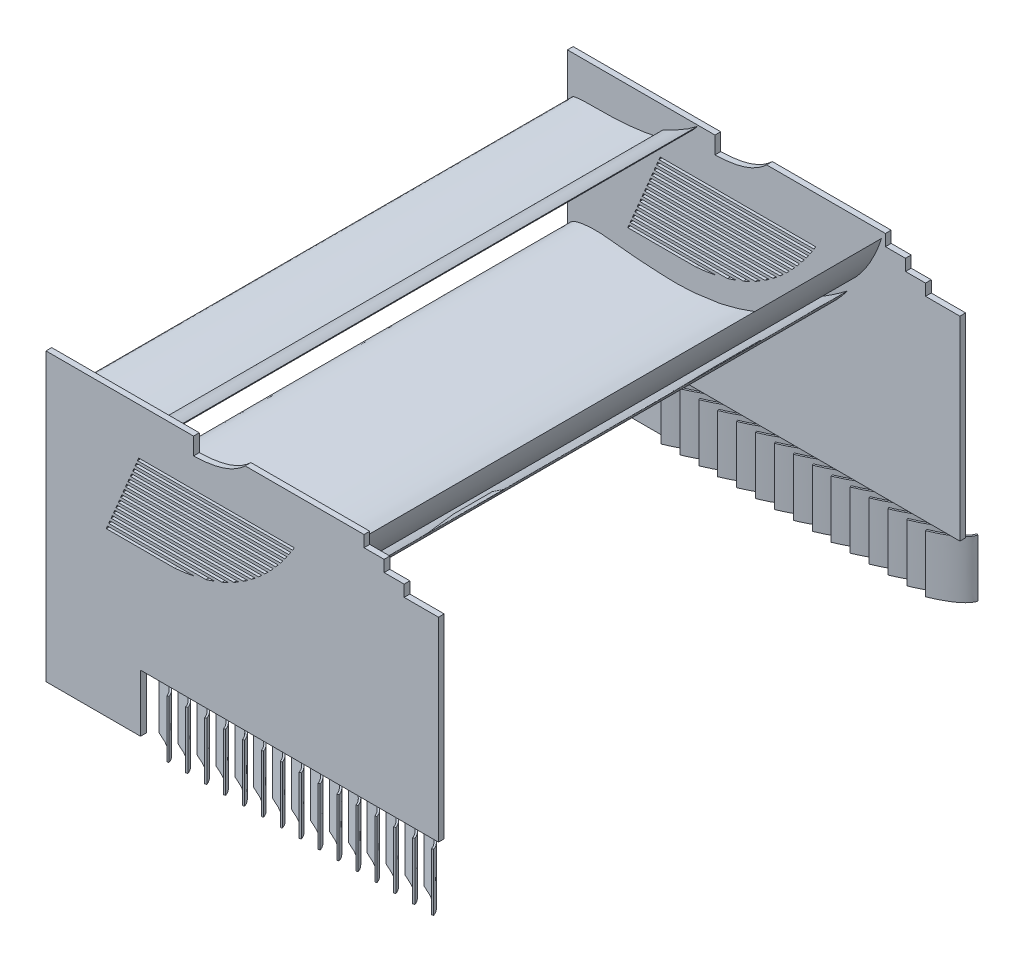
SolidWorks part; units mm, degrees
ref_plane "Front Plane" through (0, 0, 0) normal (0, 0, 1) x (1, 0, 0)
ref_plane "Top Plane" through (0, 0, 0) normal (0, 1, 0) x (1, 0, 0)
ref_plane "Right Plane" through (0, 0, 0) normal (1, 0, 0) x (0, 0, -1)
sketch "Sketch1" plane through (0, 0, 0) normal (0, 0, 1) x (1, 0, 0)
  line L0 (46.9575, 64.3181) -> (1074.8558, 208.7798) construction
sketch "Sketch2" plane through (0, 0, 0) normal (0, 0, 1) x (1, 0, 0)
  line L0 (0, 0) -> (400, 0) construction
  line L1 (0, 0) -> (399.6225, 66.8739) construction
  line L2 (0, 66.8739) -> (0, -66.8739) construction
  line L3 (10.0115, 66.8739) -> (10.0115, -116.1581) construction
  line L4 (20.0229, 66.8739) -> (20.0229, -116.1581) construction
  line L5 (30.0344, 66.8739) -> (30.0344, -116.1581) construction
  line L6 (40.0459, 66.8739) -> (40.0459, -116.1581) construction
  line L7 (50.0573, 66.8739) -> (50.0573, -116.1581) construction
  line L8 (60.0688, 66.8739) -> (60.0688, -116.1581) construction
  line L9 (70.0803, 66.8739) -> (70.0803, -116.1581) construction
  line L10 (80.0918, 66.8739) -> (80.0918, -116.1581) construction
  line L11 (90.1032, 66.8739) -> (90.1032, -116.1581) construction
  line L12 (100.1147, 66.8739) -> (100.1147, -116.1581) construction
  line L13 (110.1262, 66.8739) -> (110.1262, -116.1581) construction
  line L14 (120.1376, 66.8739) -> (120.1376, -116.1581) construction
  line L15 (130.1491, 66.8739) -> (130.1491, -116.1581) construction
  line L16 (140.1606, 66.8739) -> (140.1606, -116.1581) construction
  line L17 (150.172, 66.8739) -> (150.172, -116.1581) construction
  line L18 (160.1835, 66.8739) -> (160.1835, -116.1581) construction
  line L19 (170.195, 66.8739) -> (170.195, -116.1581) construction
  line L20 (180.2064, 66.8739) -> (180.2064, -116.1581) construction
  line L21 (190.2179, 66.8739) -> (190.2179, -116.1581) construction
  line L22 (200.2294, 66.8739) -> (200.2294, -116.1581) construction
  line L23 (210.2408, 66.8739) -> (210.2408, -116.1581) construction
  line L24 (220.2523, 66.8739) -> (220.2523, -116.1581) construction
  line L25 (230.2638, 66.8739) -> (230.2638, -116.1581) construction
  line L26 (240.2753, 66.8739) -> (240.2753, -116.1581) construction
  line L27 (250.2867, 66.8739) -> (250.2867, -116.1581) construction
  line L28 (260.2982, 66.8739) -> (260.2982, -116.1581) construction
  line L29 (270.3097, 66.8739) -> (270.3097, -116.1581) construction
  line L30 (280.3211, 66.8739) -> (280.3211, -116.1581) construction
  line L31 (290.3326, 66.8739) -> (290.3326, -116.1581) construction
  line L32 (300.3441, 66.8739) -> (300.3441, -116.1581) construction
  line L33 (310.3555, 66.8739) -> (310.3555, -116.1581) construction
  line L34 (320.367, 66.8739) -> (320.367, -116.1581) construction
  line L35 (330.3785, 66.8739) -> (330.3785, -116.1581) construction
  line L36 (340.3899, 66.8739) -> (340.3899, -116.1581) construction
  line L37 (350.4014, 66.8739) -> (350.4014, -116.1581) construction
  line L38 (360.4129, 66.8739) -> (360.4129, -116.1581) construction
  line L39 (370.4243, 66.8739) -> (370.4243, -116.1581) construction
  line L40 (380.4358, 66.8739) -> (380.4358, -116.1581) construction
  line L41 (390.4473, 66.8739) -> (390.4473, -116.1581) construction
  line L42 (400.4588, 66.8739) -> (400.4588, -116.1581) construction
  line L43 (836.1007, 66.8739) -> (-36.8556, 66.8739) construction
  line L44 (389.6225, 76.8739) -> (409.6225, 76.8739) construction
  line L45 (399.6225, 90.7703) -> (399.6225, 62.9774) construction
  line L46 (548.1427, 255.362) -> (478.7399, 156.2446) construction
  line L47 (488.7399, 146.2766) -> (482.6971, 142.1346) construction
  line L48 (389.6225, 76.8739) -> (488.7399, 146.2766) construction
  line L51 (488.7399, 194.8045) -> (488.7399, 123.7678) construction
  line L52 (478.7399, 201.6203) -> (478.7399, 116.9521) construction
  line L53 (478.7399, 156.2446) -> (614.5057, 156.2446) construction
  line L54 (389.6225, 83.3039) -> (389.6225, -27.4023) construction
  line L55 (478.7399, 146.2446) -> (614.5057, 146.2446) construction
  spline S0 degree 3 poles (8.4176, 12.2629) (-5.1, -0.6947) (8.0175, -15.4806) (19.5512, -21.724) (30.0167, -25.3022) (39.86, -28.8642) (50.0404, -30.6629) (60.0706, -32.2577) (70.0139, -34.2177) (80.101, -34.56) (90.0931, -35.3652) (100.112, -35.9529) (110.1282, -35.5072) (120.1532, -35.21) (130.1503, -34.2298) (140.19, -33.4102) (150.1782, -31.9134) (160.1704, -30.3713) (170.2408, -29.1636) (180.2083, -27.151) (190.2638, -25.3061) (200.2392, -22.8725) (210.2446, -20.4291) (220.2329, -17.8951) (230.3811, -15.7054) (240.3519, -12.3911) (253.5512, -7.3696) (266.9476, -2.8065) (280.4369, 1.6366) (290.3614, 5.8195) (300.4407, 10.0322) (310.3048, 14.8841) (323.8214, 20.8842) (337.3023, 27.2498) (350.2747, 34.8502) (364.0374, 41.2007) (378.0734, 50.4319) (389.2687, 56.9917) (404.9331, 70.6704) (388.8931, 60.8973) (380.9617, 56.8333) (370.3166, 52.1732) (360.4136, 47.7491) (350.4697, 43.0754) (340.4967, 38.8332) (330.4052, 35.261) (320.3498, 31.8494) (310.3583, 28.3259) (300.4869, 24.6622) (290.3218, 22.3006) (280.2904, 19.7619) (270.4267, 16.765) (260.336, 15.0613) (250.2769, 13.9588) (240.2662, 12.5783) (230.2787, 11.0679) (220.2867, 9.6964) (210.2433, 9.2404) (200.2287, 9.0345) (190.217, 8.2792) (180.2125, 9.1624) (170.1842, 8.7285) (160.1865, 9.5822) (150.1678, 9.9892) (140.1635, 10.7007) (130.146, 11.2145) (120.1214, 11.8409) (110.1328, 12.9697) (100.1148, 13.8501) (90.0938, 14.7159) (80.0796, 15.8427) (56.9177, 18.8475) (32.3828, 18.9634) (8.4176, 12.2629) (-5.1, -0.6947) (8.0175, -15.4806) knots -0.089629 -0.030705 -0.018228 0 0.022024 0.035622 0.048197 0.060585 0.072602 0.084545 0.096479 0.108284 0.12009 0.131879 0.143661 0.155449 0.167269 0.1791 0.190991 0.202897 0.214788 0.226766 0.238768 0.250864 0.262992 0.27512 0.287235 0.299601 0.31215 0.337082 0.349542 0.362249 0.375072 0.388091 0.40103 0.427261 0.440709 0.453892 0.481344 0.495528 0.510184 0.522428 0.535733 0.548643 0.561554 0.574511 0.587287 0.599816 0.612271 0.624763 0.637218 0.649381 0.661544 0.67375 0.685718 0.697586 0.709472 0.721375 0.733243 0.74504 0.756824 0.768611 0.780398 0.792175 0.803972 0.815766 0.827567 0.839363 0.851169 0.863006 0.874833 0.88666 0.89851 0.910371 0.969295 0.981772 1 1.022024 1.035622 1.048197 only from (0, 0) to (0, 0)
  spline S1 degree 3 poles (488.4807, 145.9571) (488.8121, 146.3498) (488.4243, 146.015) (488.0622, 145.7851) (487.2625, 145.1263) (486.2197, 144.3713) (484.8735, 143.3367) (483.2507, 142.1161) (481.3449, 140.7026) (479.1839, 139.1083) (476.7613, 137.3643) (474.1237, 135.4494) (471.2368, 133.4393) (468.1657, 131.2913) (464.8962, 129.0676) (461.4575, 126.7695) (457.874, 124.4106) (454.1513, 122.027) (450.3296, 119.6083) (446.4184, 117.1921) (442.4423, 114.7926) (438.4319, 112.4153) (434.4211, 110.0589) (430.4193, 107.7484) (426.4691, 105.4752) (422.5724, 103.27) (418.7829, 101.1054) (415.1038, 99.0189) (411.5811, 96.98) (408.2231, 95.0247) (405.0701, 93.1172) (402.1178, 91.3128) (399.4157, 89.5543) (396.9653, 87.8935) (394.7924, 86.3186) (392.9158, 84.83) (391.3498, 83.4309) (390.0835, 82.1509) (389.1526, 80.9646) (388.5665, 79.872) (388.3105, 78.8689) (388.4525, 77.9475) (389.0134, 77.2045) (389.9156, 76.685) (391.1282, 76.3842) (392.6501, 76.2546) (394.4851, 76.3138) (396.6232, 76.5794) (399.0459, 77.0357) (401.7358, 77.7205) (404.6757, 78.5968) (407.8392, 79.7049) (411.2008, 81.0269) (414.7209, 82.591) (418.3956, 84.3418) (422.1799, 86.3091) (426.0457, 88.48) (429.9704, 90.8288) (433.915, 93.3645) (437.8712, 96.0402) (441.7934, 98.8661) (445.6685, 101.7972) (449.4657, 104.8272) (453.1679, 107.924) (456.7615, 111.054) (460.2029, 114.2195) (463.5191, 117.343) (466.6501, 120.455) (469.6136, 123.4898) (472.3702, 126.4509) (474.954, 129.2656) (477.2978, 131.9605) (479.4562, 134.4635) (481.3811, 136.7846) (483.0779, 138.8974) (484.5577, 140.7696) (485.8099, 142.3825) (486.8479, 143.7389) (487.6258, 144.7686) (488.2511, 145.5957) (488.4807, 145.9571) (488.8121, 146.3498) (488.4243, 146.015) knots -0.00692 -0.003098 -0.00077 0 0.000781 0.003074 0.006931 0.012248 0.01903 0.027226 0.036785 0.04761 0.059602 0.072764 0.086897 0.102004 0.117939 0.134556 0.151858 0.169651 0.187838 0.206374 0.225065 0.243814 0.262569 0.281137 0.299514 0.317506 0.335105 0.352118 0.368488 0.384167 0.398955 0.412906 0.425872 0.437811 0.448585 0.458213 0.466669 0.473884 0.479894 0.484779 0.488743 0.492167 0.495628 0.499576 0.504487 0.510576 0.517943 0.526574 0.536524 0.54764 0.560015 0.573491 0.588031 0.603544 0.619912 0.637089 0.654944 0.673346 0.692212 0.711461 0.73091 0.750475 0.770022 0.789461 0.808651 0.827458 0.84582 0.863559 0.880666 0.896945 0.912322 0.926718 0.939993 0.952161 0.96306 0.972662 0.980906 0.987733 0.99308 0.996902 0.99923 1 1.000781 1.003074 1.006931 only from (488.7399, 146.2766) to (488.7399, 146.2766)
  spline S2 degree 3 poles (548.0012, 254.9703) (548.1874, 255.456) (547.9279, 255.0069) (547.6584, 254.6667) (547.113, 253.7707) (546.3674, 252.702) (545.4246, 251.265) (544.2794, 249.5582) (542.9279, 247.5728) (541.3924, 245.3297) (539.6567, 242.8564) (537.7725, 240.1482) (535.6814, 237.266) (533.4602, 234.1907) (531.0746, 230.977) (528.5519, 227.6359) (525.9111, 224.1885) (523.1453, 220.6711) (520.2967, 217.0873) (517.3615, 213.4761) (514.3589, 209.8593) (511.316, 206.2523) (508.2658, 202.665) (505.209, 199.1247) (502.189, 195.6372) (499.1976, 192.2326) (496.2952, 188.9024) (493.4722, 185.6835) (490.783, 182.5623) (488.2235, 179.5757) (485.844, 176.7031) (483.6219, 173.9957) (481.6239, 171.4156) (479.834, 169.0126) (478.2807, 166.784) (476.9821, 164.7365) (475.9505, 162.878) (475.1658, 161.233) (474.6707, 159.7892) (474.4739, 158.5497) (474.5629, 157.5056) (475.0053, 156.672) (475.7887, 156.1483) (476.824, 155.9518) (478.0833, 156.0678) (479.5813, 156.4503) (481.3159, 157.1174) (483.2715, 158.0828) (485.4358, 159.3251) (487.7794, 160.8747) (490.2983, 162.6906) (492.9538, 164.8026) (495.7276, 167.1848) (498.5723, 169.8513) (501.5026, 172.7478) (504.4658, 175.8877) (507.4391, 179.2493) (510.4095, 182.8005) (513.3367, 186.5371) (516.2285, 190.4114) (519.0377, 194.4179) (521.767, 198.5093) (524.3889, 202.6695) (526.8977, 206.8618) (529.2916, 211.0497) (531.5283, 215.2209) (533.6592, 219.3103) (535.617, 223.3271) (537.4402, 227.2144) (539.0902, 230.9623) (540.6237, 234.5128) (541.9677, 237.8689) (543.1982, 240.9799) (544.2661, 243.8393) (545.1852, 246.4237) (545.977, 248.7058) (546.6373, 250.6644) (547.1783, 252.3065) (547.5794, 253.5497) (547.9019, 254.5484) (548.0012, 254.9703) (548.1874, 255.456) (547.9279, 255.0069) knots -0.00692 -0.003098 -0.00077 0 0.000781 0.003074 0.006931 0.012248 0.01903 0.027226 0.036785 0.04761 0.059602 0.072764 0.086897 0.102004 0.117939 0.134556 0.151858 0.169651 0.187838 0.206374 0.225065 0.243814 0.262569 0.281137 0.299514 0.317506 0.335105 0.352118 0.368488 0.384167 0.398955 0.412906 0.425872 0.437811 0.448585 0.458213 0.466669 0.473884 0.479894 0.484779 0.488743 0.492167 0.495628 0.499576 0.504487 0.510576 0.517943 0.526574 0.536524 0.54764 0.560015 0.573491 0.588031 0.603544 0.619912 0.637089 0.654944 0.673346 0.692212 0.711461 0.73091 0.750475 0.770022 0.789461 0.808651 0.827458 0.84582 0.863559 0.880666 0.896945 0.912322 0.926718 0.939993 0.952161 0.96306 0.972662 0.980906 0.987733 0.99308 0.996902 0.99923 1 1.000781 1.003074 1.006931 only from (548.1427, 255.362) to (548.1427, 255.362)
  point P7 (0, 0)
  point P94 (399.6225, 76.8739)
  point P100 (399.6225, 76.8739)
  point P108 (399.6225, 66.8739)
  point P112 (389.6225, 76.8739)
  point P126 (488.7399, 146.2766)
  point P130 (488.7399, 156.2766)
  point P136 (488.7399, 159.2862)
  point P142 (478.7399, 159.2862)
  dimension "D1" = 9.5
  dimension "D3" = 405.1793
  dimension "D4" = 400
  dimension "D5" = 121
  dimension "D6" = 10
  dimension "D7" = 35
  dimension "D8" = 10
  dimension "D9" = 55
  dimension "D10" = 10
  dimension "D11" = 121
  dimension "D12" = 10
  dimension "D13" = 79.3707
  dimension "D2" = 41
extrude "Boss-Extrude1" add sketch "Sketch2" along normal blind 900
ref_plane "Plane1" through (0, 0, 900) normal (0, 0, 1) x (1, 0, 0)
sketch "Sketch5" plane through (0, 0, 0) normal (0, 0, 1) x (1, 0, 0)
  line L0 (555, 266.2835) -> (555, -133.7165) construction
  line L1 (0, 266.2835) -> (555, 266.2835)
  line L2 (0, 266.2835) -> (0, 0)
  line L5 (555, 266.2835) -> (555, 246.2835)
  line L6 (555, 246.2835) -> (590, 246.2835)
  line L7 (590, 246.2835) -> (590, 226.2835)
  line L8 (590, 226.2835) -> (625, 226.2835)
  line L9 (625, 226.2835) -> (625, 206.2835)
  line L10 (625, 206.2835) -> (685, 206.2835)
  line L11 (0, -233.7165) -> (165, -233.7165)
  line L13 (685, -133.7165) -> (685, 206.2835)
  line L14 (0, 0) -> (0, -233.7165)
  line L17 (165, -233.7165) -> (165, -133.7165)
  line L18 (165, -133.7165) -> (685, -133.7165)
  point P5 (0, 0)
  dimension "D1" = 500
  dimension "D2" = 685
  dimension "D3" = 35
  dimension "D4" = 20
  dimension "D5" = 20
  dimension "D6" = 35
  dimension "D7" = 20
  dimension "D8" = 60
  dimension "D9" = 100
  dimension "D10" = 520
ref_plane "Plane2" through (0, 0, 450) normal (0, 0, 1) x (1, 0, 0)
extrude "Boss-Extrude2" add sketch "Sketch5" against normal blind 10 contours L1 L5 L6 L7 L8 L9 L10 L13 L18 L17 L11 L14 L2
sketch "Sketch6" plane through (0, 0, 0) normal (0, 0, 1) x (1, 0, 0)
  line L0 (0, 197.4544) -> (160, 197.4544) construction
  line L1 (0, 266.2835) -> (0, 0) construction
  line L2 (160, 197.4544) -> (258.2982, 266.2835) construction
  line L3 (0, 266.2835) -> (555, 266.2835) construction
  line L4 (164.6138, 214.9761) -> (164.7238, 214.6645)
  line L5 (164.6138, 214.9761) -> (8.3018, 197.4544) construction
  line L6 (8.3018, 197.4544) -> (160, 197.4544) construction
  line L7 (164.7238, 214.6645) -> (215.8682, 214.6645) construction
  line L8 (164.6138, 224.6645) -> (215.8682, 224.6645) construction
  line L9 (227.0142, 264.2269) -> (227.1245, 264.1177)
  line L10 (227.0142, 264.2269) -> (164.4495, 224.8752) construction
  spline S0 degree 3 poles (164.7238, 214.6645) (164.6485, 214.6279) (164.3478, 214.4816) (163.6724, 214.1552) (162.55, 213.6175) (160.9852, 212.8783) (158.985, 211.9502) (156.5581, 210.8501) (153.7156, 209.5966) (150.4706, 208.2115) (146.8388, 206.7177) (142.8379, 205.1402) (138.4882, 203.505) (133.8122, 201.8376) (128.8347, 200.165) (123.5829, 198.5127) (118.0862, 196.9059) (112.3762, 195.3683) (106.4862, 193.9228) (100.4517, 192.5894) (94.3097, 191.3873) (88.0988, 190.332) (81.8589, 189.4374) (75.6309, 188.7132) (69.4566, 188.1671) (63.3778, 187.8027) (57.4367, 187.6199) (51.6745, 187.6158) (46.1317, 187.7835) (40.8475, 188.1122) (35.859, 188.5889) (31.201, 189.198) (26.9054, 189.9203) (23.0013, 190.7368) (19.5141, 191.6263) (16.4656, 192.568) (13.8731, 193.5412) (11.7498, 194.5273) (10.1003, 195.5106) (8.9257, 196.4838) (8.2062, 197.4661) (8.027, 198.5089) (8.4702, 199.4674) (9.4095, 200.2316) (10.7736, 200.88) (12.5817, 201.4358) (14.8279, 201.9066) (17.5019, 202.295) (20.5864, 202.6069) (24.0614, 202.8473) (27.9044, 203.0253) (32.0912, 203.1493) (36.5959, 203.231) (41.3918, 203.282) (46.4505, 203.3154) (51.7431, 203.3445) (57.2393, 203.3835) (62.9083, 203.4456) (68.7179, 203.5435) (74.6355, 203.6891) (80.6273, 203.8921) (86.6588, 204.1602) (92.6952, 204.4989) (98.701, 204.9104) (104.6405, 205.3951) (110.4779, 205.9495) (116.1778, 206.5676) (121.7051, 207.2412) (127.0255, 207.9592) (132.1056, 208.7094) (136.9131, 209.4769) (141.4173, 210.2472) (145.589, 211.0042) (149.4009, 211.7324) (152.8279, 212.4165) (155.8468, 213.0419) (158.4374, 213.5952) (160.5819, 214.065) (162.2656, 214.441) (163.4767, 214.7155) (164.2068, 214.8826) (164.5322, 214.9574) (164.6138, 214.9761) knots 0 0 0 0 0.00078 0.003113 0.006984 0.012366 0.019224 0.027511 0.037173 0.048145 0.060358 0.073731 0.088182 0.103618 0.119946 0.137065 0.15487 0.173257 0.192113 0.211327 0.230786 0.250373 0.269972 0.289465 0.308737 0.32767 0.346151 0.364066 0.381307 0.397768 0.413347 0.427952 0.441493 0.45389 0.465074 0.474985 0.48358 0.490835 0.496756 0.501407 0.504969 0.507873 0.510777 0.514327 0.518939 0.524778 0.531895 0.540287 0.549922 0.560751 0.572712 0.585736 0.599745 0.614657 0.630386 0.646842 0.66393 0.681556 0.699621 0.718024 0.736663 0.755434 0.774231 0.792948 0.811476 0.829709 0.847536 0.864851 0.881546 0.897515 0.912656 0.926869 0.940056 0.952128 0.962998 0.972589 0.98083 0.98766 0.993027 0.996891 0.999221 1 1 1 1
  spline S1 degree 3 poles (227.1245, 264.1177) (227.1002, 264.0868) (227.003, 263.9634) (226.7842, 263.6871) (226.4198, 263.23) (225.9096, 262.5971) (225.2539, 261.7952) (224.4531, 260.8332) (223.508, 259.7213) (222.4196, 258.4713) (221.1899, 257.0962) (219.8214, 255.6101) (218.3172, 254.0282) (216.6816, 252.3659) (214.9197, 250.6397) (213.0376, 248.8659) (211.0426, 247.0612) (208.9433, 245.2421) (206.749, 243.4251) (204.4708, 241.6258) (202.1201, 239.8601) (199.7103, 238.1424) (197.2553, 236.4866) (194.7705, 234.9053) (192.2719, 233.4103) (189.7765, 232.0117) (187.302, 230.7181) (184.8667, 229.5366) (182.489, 228.4727) (180.1876, 227.5298) (177.9809, 226.71) (175.8869, 226.0139) (173.9229, 225.4398) (172.1051, 224.9857) (170.4487, 224.6478) (168.967, 224.4218) (167.6717, 224.3024) (166.5721, 224.2846) (165.6734, 224.3626) (164.9776, 224.5336) (164.4722, 224.8016) (164.183, 225.2058) (164.1741, 225.7018) (164.4148, 226.2172) (164.8587, 226.7706) (165.5094, 227.3758) (166.3627, 228.0347) (167.4137, 228.7464) (168.6539, 229.5097) (170.0739, 230.3229) (171.6622, 231.1849) (173.4069, 232.0945) (175.2947, 233.0513) (177.3119, 234.0548) (179.4438, 235.1046) (181.6755, 236.2005) (183.9912, 237.3423) (186.3753, 238.5292) (188.8115, 239.76) (191.2835, 241.0331) (193.7752, 242.3457) (196.2704, 243.6939) (198.7531, 245.073) (201.208, 246.4765) (203.6199, 247.8975) (205.9744, 249.327) (208.2576, 250.7553) (210.4566, 252.1717) (212.559, 253.5646) (214.5532, 254.9218) (216.4286, 256.2306) (218.1752, 257.4784) (219.784, 258.6526) (221.2465, 259.7409) (222.5553, 260.7317) (223.7036, 261.6142) (224.6856, 262.3786) (225.4961, 263.0162) (226.131, 263.5199) (226.5868, 263.8839) (226.8612, 264.104) (226.9835, 264.2023) (227.0142, 264.2269) knots 0 0 0 0 0.00078 0.003113 0.006984 0.012366 0.019224 0.027511 0.037173 0.048145 0.060358 0.073731 0.088182 0.103618 0.119946 0.137065 0.15487 0.173257 0.192113 0.211327 0.230786 0.250373 0.269972 0.289465 0.308737 0.32767 0.346151 0.364066 0.381307 0.397768 0.413347 0.427952 0.441493 0.45389 0.465074 0.474985 0.48358 0.490835 0.496756 0.501407 0.504969 0.507873 0.510777 0.514327 0.518939 0.524778 0.531895 0.540287 0.549922 0.560751 0.572712 0.585736 0.599745 0.614657 0.630386 0.646842 0.66393 0.681556 0.699621 0.718024 0.736663 0.755434 0.774231 0.792948 0.811476 0.829709 0.847536 0.864851 0.881546 0.897515 0.912656 0.926869 0.940056 0.952128 0.962998 0.972589 0.98083 0.98766 0.993027 0.996891 0.999221 1 1 1 1
  dimension "D1" = 145
  dimension "D2" = 160
  dimension "D3" = 120
  dimension "D4" = 10
extrude "Boss-Extrude3" add sketch "Sketch6" along normal blind 900
sketch "Sketch7" plane through (0, 0, 0) normal (0, 0, 1) x (1, 0, 0)
  line L0 (257.5301, 266.2835) -> (257.5301, 236.2835)
  line L1 (0, 266.2835) -> (555, 266.2835) construction
  line L2 (257.5301, 266.2835) -> (347.5301, 266.2835)
  line L3 (347.5301, 266.2835) -> (317.5714, 237.211) construction
  line L4 (317.5714, 237.211) -> (257.5301, 236.2835) construction
  spline S1 degree 2 poles (347.5301, 266.2835) (317.5714, 237.211) (257.5301, 236.2835) knots 0 0 0 1 1 1
  dimension "D1" = 30
  dimension "D2" = 90
extrude "Cut-Extrude1" cut sketch "Sketch7" against normal blind 900
sketch "Sketch8" plane through (0, 0, 0) normal (0, 0, 1) x (1, 0, 0)
  line L4 (161.8037, 185.2784) -> (433.5275, 185.2784)
  line L5 (159.7086, 180.2784) -> (430.4208, 180.2784)
  line L16 (164.9224, 130.2784) -> (452.6678, 130.2784) [skipped]
  line L26 (67.2058, 135.2784) -> (220.4617, 135.2784) [skipped]
  line L27 (76.1878, 140.2784) -> (244.1181, 140.2784) [skipped]
  line L28 (85.1699, 145.2784) -> (267.7746, 145.2784) [skipped]
  line L29 (94.1519, 150.2784) -> (291.431, 150.2784) [skipped]
  line L30 (103.1339, 155.2784) -> (315.0875, 155.2784) [skipped]
  line L31 (112.116, 160.2784) -> (338.7439, 160.2784) [skipped]
  line L32 (121.098, 165.2784) -> (362.4003, 165.2784) [skipped]
  line L33 (139.0621, 175.2784) -> (409.7132, 175.2784) [skipped]
  line L34 (130.08, 170.2784) -> (386.0568, 170.2784) [skipped]
  line L36 (155.5185, 170.2784) -> (423.8746, 170.2784)
  line L37 (157.6135, 175.2784) -> (427.2053, 175.2784)
  line L40 (151.3284, 160.2784) -> (416.8376, 160.2784)
  line L41 (153.4234, 165.2784) -> (420.4214, 165.2784)
  line L44 (147.1382, 150.2784) -> (409.2419, 150.2784)
  line L45 (149.2333, 155.2784) -> (413.1145, 155.2784)
  line L48 (142.9481, 140.2784) -> (401.0022, 140.2784)
  line L49 (145.0432, 145.2784) -> (405.2087, 145.2784)
  line L52 (138.758, 130.2784) -> (392.0089, 130.2784)
  line L53 (140.853, 135.2784) -> (396.6078, 135.2784)
  line L56 (134.5679, 120.2784) -> (382.1176, 120.2784)
  line L57 (136.6629, 125.2784) -> (387.1863, 125.2784)
  line L60 (130.3777, 110.2784) -> (371.1304, 110.2784)
  line L61 (132.4728, 115.2784) -> (376.7761, 115.2784)
  line L64 (126.1876, 100.2784) -> (358.7645, 100.2784)
  line L65 (128.2827, 105.2784) -> (365.1422, 105.2784)
  line L68 (121.9975, 90.2784) -> (344.5889, 90.2784)
  line L69 (124.0926, 95.2784) -> (351.9385, 95.2784)
  line L72 (117.8074, 80.2784) -> (327.8864, 80.2784)
  line L73 (119.9024, 85.2784) -> (336.6165, 85.2784)
  line L76 (113.6173, 70.2784) -> (307.2861, 70.2784)
  line L77 (115.7123, 75.2784) -> (318.2064, 75.2784)
  line L80 (109.4271, 60.2784) -> (279.3938, 60.2784)
  line L81 (111.5222, 65.2784) -> (294.6475, 65.2784)
  line L84 (105.237, 50.2784) -> (224.5387, 50.2784)
  line L85 (107.3321, 55.2784) -> (259.3865, 55.2784)
  line L88 (161.8037, 185.2784) -> (159.7086, 180.2784)
  line L89 (119.9024, 85.2784) -> (117.8074, 80.2784)
  line L114 (107.3321, 55.2784) -> (105.237, 50.2784)
  line L115 (111.5222, 65.2784) -> (109.4271, 60.2784)
  line L116 (115.7123, 75.2784) -> (113.6173, 70.2784)
  line L117 (124.0926, 95.2784) -> (121.9975, 90.2784)
  line L118 (128.2827, 105.2784) -> (126.1876, 100.2784)
  line L119 (132.4728, 115.2784) -> (130.3777, 110.2784)
  line L120 (157.6135, 175.2784) -> (155.5185, 170.2784)
  line L121 (153.4234, 165.2784) -> (151.3284, 160.2784)
  line L122 (149.2333, 155.2784) -> (147.1382, 150.2784)
  line L123 (145.0432, 145.2784) -> (142.9481, 140.2784)
  line L124 (140.853, 135.2784) -> (138.758, 130.2784)
  line L125 (136.6629, 125.2784) -> (134.5679, 120.2784)
  spline S0 degree 2 poles (433.5275, 185.2784) (431.986, 182.755) (430.4208, 180.2784) knots 0 0 0 0.017044 0.017044 0.017044
  spline S1 degree 3 poles (420.4214, 165.2784) (419.2361, 163.5933) (418.0415, 161.9267) (416.8376, 160.2784) knots 0.070227 0.070227 0.070227 0.070227 0.088712 0.088712 0.088712 0.088712
  spline S2 degree 3 poles (427.2053, 175.2784) (426.1036, 173.5948) (424.9934, 171.9282) (423.8746, 170.2784) knots 0.034417 0.034417 0.034417 0.034417 0.052137 0.052137 0.052137 0.052137
  spline S3 degree 3 poles (413.1145, 155.2784) (411.8338, 153.5916) (410.543, 151.9249) (409.2419, 150.2784) knots 0.107617 0.107617 0.107617 0.107617 0.126974 0.126974 0.126974 0.126974
  spline S4 degree 3 poles (405.2087, 145.2784) (403.8178, 143.5894) (402.4157, 141.9228) (401.0022, 140.2784) knots 0.146816 0.146816 0.146816 0.146816 0.167181 0.167181 0.167181 0.167181
  spline S5 degree 3 poles (396.6078, 135.2784) (395.0875, 133.5868) (393.5545, 131.9201) (392.0089, 130.2784) knots 0.188113 0.188113 0.188113 0.188113 0.209663 0.209663 0.209663 0.209663
  spline S6 degree 3 poles (387.1863, 125.2784) (385.5111, 123.5834) (383.8215, 121.9167) (382.1176, 120.2784) knots 0.231889 0.231889 0.231889 0.231889 0.254857 0.254857 0.254857 0.254857
  spline S7 degree 3 poles (376.7761, 115.2784) (374.9109, 113.5789) (373.029, 111.9122) (371.1304, 110.2784) knots 0.27865 0.27865 0.27865 0.27865 0.303361 0.303361 0.303361 0.303361
  spline S8 degree 3 poles (365.1422, 105.2784) (363.0361, 103.5728) (360.9102, 101.9061) (358.7645, 100.2784) knots 0.329106 0.329106 0.329106 0.329106 0.356027 0.356027 0.356027 0.356027
  spline S9 degree 3 poles (351.9385, 95.2784) (349.5129, 93.5638) (347.0631, 91.8972) (344.5889, 90.2784) knots 0.384302 0.384302 0.384302 0.384302 0.414159 0.414159 0.414159 0.414159
  spline S10 degree 3 poles (336.6165, 85.2784) (333.738, 83.5495) (330.828, 81.8829) (327.8864, 80.2784) knots 0.445896 0.445896 0.445896 0.445896 0.47992 0.47992 0.47992 0.47992
  spline S11 degree 3 poles (318.2064, 75.2784) (314.6113, 73.523) (310.9712, 71.8563) (307.2861, 70.2784) knots 0.516814 0.516814 0.516814 0.516814 0.557452 0.557452 0.557452 0.557452
  spline S12 degree 3 poles (294.6475, 65.2784) (289.6416, 63.4567) (284.557, 61.79) (279.3938, 60.2784) knots 0.60328 0.60328 0.60328 0.60328 0.657004 0.657004 0.657004 0.657004
  spline S13 degree 3 poles (259.3865, 55.2784) (248.1179, 52.9273) (236.502, 51.2606) (224.5387, 50.2784) knots 0.725082 0.725082 0.725082 0.725082 0.837974 0.837974 0.837974 0.837974
  dimension "D1" = 14
  dimension "D6" = 12
extrude "Cut-Extrude2" cut sketch "Sketch8" against normal blind 900
ref_plane "Plane3" through (170, 0, 0) normal (-1, 0, 0) x (0, 0, 1)
sketch "Sketch9" plane through (170, 0, 0) normal (-1, 0, 0) x (0, 0, 1)
  line L7 (-22.6284, -233.2472) -> (-20.6284, -233.2472)
  point P1 (-10, -113.3858)
  point P3 (-10, -111.7165)
ref_plane "Plane4" through (0, -170, 0) normal (0, -1, 0) x (-1, 0, 0)
sketch "Sketch18" plane through (0, -133.7165, 0) normal (0, -1, 0) x (1, 0, 0)
  line L0 (165, 0) -> (165, -10) construction
  line L1 (165, -10) -> (165, -5) construction
  line L2 (165, -5) -> (685, -5) construction
  line L3 (685, -10) -> (685, 0) construction
  line L4 (177.3877, 14.0501) -> (223.6164, -5) construction
  line L5 (223.6164, -5) -> (229.5712, -25) construction
  line L6 (210.3877, 14.0501) -> (209.2447, 11.2764)
  line L7 (177.3877, 14.0501) -> (176.2447, 11.2764)
  line L8 (226.6959, -25.8561) -> (229.5712, -25)
  line L9 (181.902, 0) -> (181.902, -10) construction
  line L10 (165, 0) -> (685, 0) construction
  line L11 (165, -10) -> (685, -10) construction
  line L14 (259.6959, -25.8561) -> (262.5712, -25)
  line L15 (210.3877, 14.0501) -> (256.6164, -5) construction
  line L18 (256.6164, -5) -> (262.5712, -25) construction
  line L19 (243.3877, 14.0501) -> (242.2447, 11.2764)
  line L22 (292.6959, -25.8561) -> (295.5712, -25)
  line L23 (243.3877, 14.0501) -> (289.6164, -5) construction
  line L26 (289.6164, -5) -> (295.5712, -25) construction
  line L27 (276.3877, 14.0501) -> (275.2447, 11.2764)
  line L30 (325.6959, -25.8561) -> (328.5712, -25)
  line L31 (276.3877, 14.0501) -> (322.6164, -5) construction
  line L34 (322.6164, -5) -> (328.5712, -25) construction
  line L35 (309.3877, 14.0501) -> (308.2447, 11.2764)
  line L38 (358.6959, -25.8561) -> (361.5712, -25)
  line L39 (309.3877, 14.0501) -> (355.6164, -5) construction
  line L42 (355.6164, -5) -> (361.5712, -25) construction
  line L43 (342.3877, 14.0501) -> (341.2447, 11.2764)
  line L46 (391.6959, -25.8561) -> (394.5712, -25)
  line L47 (342.3877, 14.0501) -> (388.6164, -5) construction
  line L50 (388.6164, -5) -> (394.5712, -25) construction
  line L51 (375.3877, 14.0501) -> (374.2447, 11.2764)
  line L54 (424.6959, -25.8561) -> (427.5712, -25)
  line L55 (375.3877, 14.0501) -> (421.6164, -5) construction
  line L58 (421.6164, -5) -> (427.5712, -25) construction
  line L59 (408.3877, 14.0501) -> (407.2447, 11.2764)
  line L62 (457.6959, -25.8561) -> (460.5712, -25)
  line L63 (408.3877, 14.0501) -> (454.6164, -5) construction
  line L66 (454.6164, -5) -> (460.5712, -25) construction
  line L67 (441.3877, 14.0501) -> (440.2447, 11.2764)
  line L68 (490.6959, -25.8561) -> (493.5712, -25)
  line L69 (441.3877, 14.0501) -> (487.6164, -5) construction
  line L70 (487.6164, -5) -> (493.5712, -25) construction
  line L71 (474.3877, 14.0501) -> (473.2447, 11.2764)
  line L72 (523.6959, -25.8561) -> (526.5712, -25)
  line L73 (474.3877, 14.0501) -> (520.6164, -5) construction
  line L74 (520.6164, -5) -> (526.5712, -25) construction
  line L75 (507.3877, 14.0501) -> (506.2447, 11.2764)
  line L76 (556.6959, -25.8561) -> (559.5712, -25)
  line L77 (507.3877, 14.0501) -> (553.6164, -5) construction
  line L78 (553.6164, -5) -> (559.5712, -25) construction
  line L79 (540.3877, 14.0501) -> (539.2447, 11.2764)
  line L80 (589.6959, -25.8561) -> (592.5712, -25)
  line L81 (540.3877, 14.0501) -> (586.6164, -5) construction
  line L82 (586.6164, -5) -> (592.5712, -25) construction
  line L83 (573.3877, 14.0501) -> (572.2447, 11.2764)
  line L84 (622.6959, -25.8561) -> (625.5712, -25)
  line L85 (573.3877, 14.0501) -> (619.6164, -5) construction
  line L86 (619.6164, -5) -> (625.5712, -25) construction
  line L87 (606.3877, 14.0501) -> (605.2447, 11.2764)
  line L88 (655.6959, -25.8561) -> (658.5712, -25)
  line L89 (606.3877, 14.0501) -> (652.6164, -5) construction
  line L90 (652.6164, -5) -> (658.5712, -25) construction
  line L91 (639.3877, 14.0501) -> (638.2447, 11.2764)
  line L92 (688.6959, -25.8561) -> (691.5712, -25)
  line L93 (639.3877, 14.0501) -> (685.6164, -5) construction
  line L94 (685.6164, -5) -> (691.5712, -25) construction
  spline S0 degree 2 poles (177.3877, 14.0501) (223.6164, -5) (229.5712, -25) knots 0 0 0 1 1 1
  spline S1 degree 1 poles (176.2447, 11.2764) (226.6959, -25.8561) knots 0 0 1 1 construction
  spline S2 degree 3 poles (176.2447, 11.2764) (177.1871, 10.888) (179.0843, 10.0949) (182.7314, 8.5242) (187.1043, 6.5528) (192.0253, 4.187) (198.1605, 1.0294) (205.024, -2.9187) (211.9669, -7.6449) (217.6113, -12.3382) (221.2342, -16.1946) (223.4953, -19.2284) (224.8776, -21.4694) (225.9598, -23.6908) (226.4755, -25.1158) (226.6959, -25.8561) knots 0 0 0 0 0.03125 0.0625 0.125 0.1875 0.25 0.375 0.5 0.625 0.75 0.8125 0.875 0.9375 1 1 1 1
  spline S3 degree 2 poles (210.3877, 14.0501) (256.6164, -5) (262.5712, -25) knots 0 0 0 1 1 1
  spline S4 degree 3 poles (209.2447, 11.2764) (210.1871, 10.888) (212.0843, 10.0949) (215.7314, 8.5242) (220.1043, 6.5528) (225.0253, 4.187) (231.1605, 1.0294) (238.024, -2.9187) (244.9669, -7.6449) (250.6113, -12.3382) (254.2342, -16.1946) (256.4953, -19.2284) (257.8776, -21.4694) (258.9598, -23.6908) (259.4755, -25.1158) (259.6959, -25.8561) knots 0 0 0 0 0.03125 0.0625 0.125 0.1875 0.25 0.375 0.5 0.625 0.75 0.8125 0.875 0.9375 1 1 1 1
  spline S5 degree 2 poles (243.3877, 14.0501) (289.6164, -5) (295.5712, -25) knots 0 0 0 1 1 1
  spline S6 degree 3 poles (242.2447, 11.2764) (243.1871, 10.888) (245.0843, 10.0949) (248.7314, 8.5242) (253.1043, 6.5528) (258.0253, 4.187) (264.1605, 1.0294) (271.024, -2.9187) (277.9669, -7.6449) (283.6113, -12.3382) (287.2342, -16.1946) (289.4953, -19.2284) (290.8776, -21.4694) (291.9598, -23.6908) (292.4755, -25.1158) (292.6959, -25.8561) knots 0 0 0 0 0.03125 0.0625 0.125 0.1875 0.25 0.375 0.5 0.625 0.75 0.8125 0.875 0.9375 1 1 1 1
  spline S7 degree 2 poles (276.3877, 14.0501) (322.6164, -5) (328.5712, -25) knots 0 0 0 1 1 1
  spline S8 degree 3 poles (275.2447, 11.2764) (276.1871, 10.888) (278.0843, 10.0949) (281.7314, 8.5242) (286.1043, 6.5528) (291.0253, 4.187) (297.1605, 1.0294) (304.024, -2.9187) (310.9669, -7.6449) (316.6113, -12.3382) (320.2342, -16.1946) (322.4953, -19.2284) (323.8776, -21.4694) (324.9598, -23.6908) (325.4755, -25.1158) (325.6959, -25.8561) knots 0 0 0 0 0.03125 0.0625 0.125 0.1875 0.25 0.375 0.5 0.625 0.75 0.8125 0.875 0.9375 1 1 1 1
  spline S9 degree 2 poles (309.3877, 14.0501) (355.6164, -5) (361.5712, -25) knots 0 0 0 1 1 1
  spline S10 degree 3 poles (308.2447, 11.2764) (309.1871, 10.888) (311.0843, 10.0949) (314.7314, 8.5242) (319.1043, 6.5528) (324.0253, 4.187) (330.1605, 1.0294) (337.024, -2.9187) (343.9669, -7.6449) (349.6113, -12.3382) (353.2342, -16.1946) (355.4953, -19.2284) (356.8776, -21.4694) (357.9598, -23.6908) (358.4755, -25.1158) (358.6959, -25.8561) knots 0 0 0 0 0.03125 0.0625 0.125 0.1875 0.25 0.375 0.5 0.625 0.75 0.8125 0.875 0.9375 1 1 1 1
  spline S11 degree 2 poles (342.3877, 14.0501) (388.6164, -5) (394.5712, -25) knots 0 0 0 1 1 1
  spline S12 degree 3 poles (341.2447, 11.2764) (342.1871, 10.888) (344.0843, 10.0949) (347.7314, 8.5242) (352.1043, 6.5528) (357.0253, 4.187) (363.1605, 1.0294) (370.024, -2.9187) (376.9669, -7.6449) (382.6113, -12.3382) (386.2342, -16.1946) (388.4953, -19.2284) (389.8776, -21.4694) (390.9598, -23.6908) (391.4755, -25.1158) (391.6959, -25.8561) knots 0 0 0 0 0.03125 0.0625 0.125 0.1875 0.25 0.375 0.5 0.625 0.75 0.8125 0.875 0.9375 1 1 1 1
  spline S13 degree 2 poles (375.3877, 14.0501) (421.6164, -5) (427.5712, -25) knots 0 0 0 1 1 1
  spline S14 degree 3 poles (374.2447, 11.2764) (375.1871, 10.888) (377.0843, 10.0949) (380.7314, 8.5242) (385.1043, 6.5528) (390.0253, 4.187) (396.1605, 1.0294) (403.024, -2.9187) (409.9669, -7.6449) (415.6113, -12.3382) (419.2342, -16.1946) (421.4953, -19.2284) (422.8776, -21.4694) (423.9598, -23.6908) (424.4755, -25.1158) (424.6959, -25.8561) knots 0 0 0 0 0.03125 0.0625 0.125 0.1875 0.25 0.375 0.5 0.625 0.75 0.8125 0.875 0.9375 1 1 1 1
  spline S15 degree 2 poles (408.3877, 14.0501) (454.6164, -5) (460.5712, -25) knots 0 0 0 1 1 1
  spline S16 degree 3 poles (407.2447, 11.2764) (408.1871, 10.888) (410.0843, 10.0949) (413.7314, 8.5242) (418.1043, 6.5528) (423.0253, 4.187) (429.1605, 1.0294) (436.024, -2.9187) (442.9669, -7.6449) (448.6113, -12.3382) (452.2342, -16.1946) (454.4953, -19.2284) (455.8776, -21.4694) (456.9598, -23.6908) (457.4755, -25.1158) (457.6959, -25.8561) knots 0 0 0 0 0.03125 0.0625 0.125 0.1875 0.25 0.375 0.5 0.625 0.75 0.8125 0.875 0.9375 1 1 1 1
  spline S17 degree 2 poles (441.3877, 14.0501) (487.6164, -5) (493.5712, -25) knots 0 0 0 1 1 1
  spline S18 degree 3 poles (440.2447, 11.2764) (441.1871, 10.888) (443.0843, 10.0949) (446.7314, 8.5242) (451.1043, 6.5528) (456.0253, 4.187) (462.1605, 1.0294) (469.024, -2.9187) (475.9669, -7.6449) (481.6113, -12.3382) (485.2342, -16.1946) (487.4953, -19.2284) (488.8776, -21.4694) (489.9598, -23.6908) (490.4755, -25.1158) (490.6959, -25.8561) knots 0 0 0 0 0.03125 0.0625 0.125 0.1875 0.25 0.375 0.5 0.625 0.75 0.8125 0.875 0.9375 1 1 1 1
  spline S19 degree 2 poles (474.3877, 14.0501) (520.6164, -5) (526.5712, -25) knots 0 0 0 1 1 1
  spline S20 degree 3 poles (473.2447, 11.2764) (474.1871, 10.888) (476.0843, 10.0949) (479.7314, 8.5242) (484.1043, 6.5528) (489.0253, 4.187) (495.1605, 1.0294) (502.024, -2.9187) (508.9669, -7.6449) (514.6113, -12.3382) (518.2342, -16.1946) (520.4953, -19.2284) (521.8776, -21.4694) (522.9598, -23.6908) (523.4755, -25.1158) (523.6959, -25.8561) knots 0 0 0 0 0.03125 0.0625 0.125 0.1875 0.25 0.375 0.5 0.625 0.75 0.8125 0.875 0.9375 1 1 1 1
  spline S21 degree 2 poles (507.3877, 14.0501) (553.6164, -5) (559.5712, -25) knots 0 0 0 1 1 1
  spline S22 degree 3 poles (506.2447, 11.2764) (507.1871, 10.888) (509.0843, 10.0949) (512.7314, 8.5242) (517.1043, 6.5528) (522.0253, 4.187) (528.1605, 1.0294) (535.024, -2.9187) (541.9669, -7.6449) (547.6113, -12.3382) (551.2342, -16.1946) (553.4953, -19.2284) (554.8776, -21.4694) (555.9598, -23.6908) (556.4755, -25.1158) (556.6959, -25.8561) knots 0 0 0 0 0.03125 0.0625 0.125 0.1875 0.25 0.375 0.5 0.625 0.75 0.8125 0.875 0.9375 1 1 1 1
  spline S23 degree 2 poles (540.3877, 14.0501) (586.6164, -5) (592.5712, -25) knots 0 0 0 1 1 1
  spline S24 degree 3 poles (539.2447, 11.2764) (540.1871, 10.888) (542.0843, 10.0949) (545.7314, 8.5242) (550.1043, 6.5528) (555.0253, 4.187) (561.1605, 1.0294) (568.024, -2.9187) (574.9669, -7.6449) (580.6113, -12.3382) (584.2342, -16.1946) (586.4953, -19.2284) (587.8776, -21.4694) (588.9598, -23.6908) (589.4755, -25.1158) (589.6959, -25.8561) knots 0 0 0 0 0.03125 0.0625 0.125 0.1875 0.25 0.375 0.5 0.625 0.75 0.8125 0.875 0.9375 1 1 1 1
  spline S25 degree 2 poles (573.3877, 14.0501) (619.6164, -5) (625.5712, -25) knots 0 0 0 1 1 1
  spline S26 degree 3 poles (572.2447, 11.2764) (573.1871, 10.888) (575.0843, 10.0949) (578.7314, 8.5242) (583.1043, 6.5528) (588.0253, 4.187) (594.1605, 1.0294) (601.024, -2.9187) (607.9669, -7.6449) (613.6113, -12.3382) (617.2342, -16.1946) (619.4953, -19.2284) (620.8776, -21.4694) (621.9598, -23.6908) (622.4755, -25.1158) (622.6959, -25.8561) knots 0 0 0 0 0.03125 0.0625 0.125 0.1875 0.25 0.375 0.5 0.625 0.75 0.8125 0.875 0.9375 1 1 1 1
  spline S27 degree 2 poles (606.3877, 14.0501) (652.6164, -5) (658.5712, -25) knots 0 0 0 1 1 1
  spline S28 degree 3 poles (605.2447, 11.2764) (606.1871, 10.888) (608.0843, 10.0949) (611.7314, 8.5242) (616.1043, 6.5528) (621.0253, 4.187) (627.1605, 1.0294) (634.024, -2.9187) (640.9669, -7.6449) (646.6113, -12.3382) (650.2342, -16.1946) (652.4953, -19.2284) (653.8776, -21.4694) (654.9598, -23.6908) (655.4755, -25.1158) (655.6959, -25.8561) knots 0 0 0 0 0.03125 0.0625 0.125 0.1875 0.25 0.375 0.5 0.625 0.75 0.8125 0.875 0.9375 1 1 1 1
  spline S29 degree 2 poles (639.3877, 14.0501) (685.6164, -5) (691.5712, -25) knots 0 0 0 1 1 1
  spline S30 degree 3 poles (638.2447, 11.2764) (639.1871, 10.888) (641.0843, 10.0949) (644.7314, 8.5242) (649.1043, 6.5528) (654.0253, 4.187) (660.1605, 1.0294) (667.024, -2.9187) (673.9669, -7.6449) (679.6113, -12.3382) (683.2342, -16.1946) (685.4953, -19.2284) (686.8776, -21.4694) (687.9598, -23.6908) (688.4755, -25.1158) (688.6959, -25.8561) knots 0 0 0 0 0.03125 0.0625 0.125 0.1875 0.25 0.375 0.5 0.625 0.75 0.8125 0.875 0.9375 1 1 1 1
  dimension "D2" = 50
  dimension "D3" = 20
  dimension "D1" = 3
extrude "Boss-Extrude5" add sketch "Sketch18" along normal blind 100
mirror "Mirror1" about plane through (0, 0, 450) normal (0, 0, 1) of "Boss-Extrude5", "Boss-Extrude2", "Cut-Extrude1", "Cut-Extrude2"
